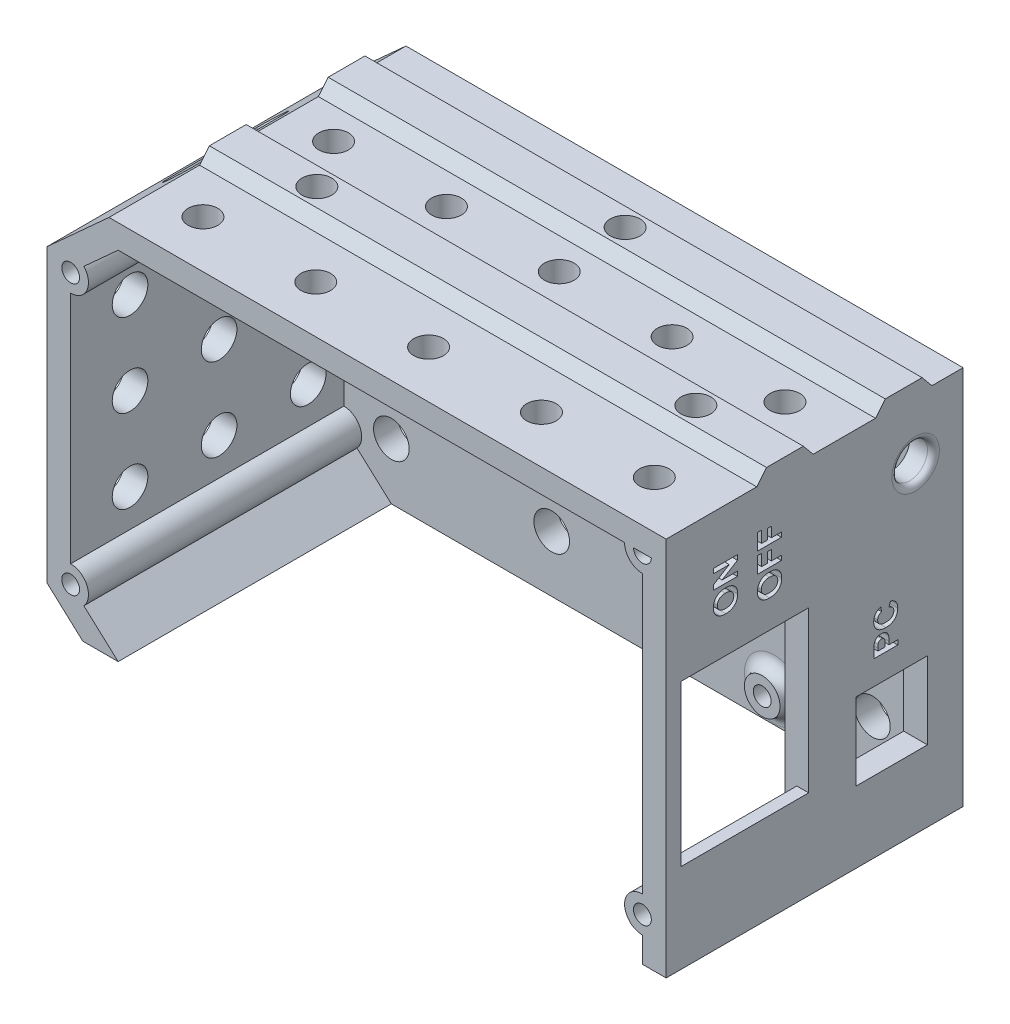
SolidWorks part; units mm, degrees
ref_plane "Спереди" through (0, 0, 0) normal (0, 0, 1) x (1, 0, 0)
ref_plane "Сверху" through (0, 0, 0) normal (0, 1, 0) x (1, 0, 0)
ref_plane "Справа" through (0, 0, 0) normal (1, 0, 0) x (0, 0, -1)
sketch "Эскиз1" plane through (0, 0, 0) normal (0, 0, 1) x (1, 0, 0)
  line L1 (-45, 30) -> (45, 30)
  line L2 (-45, 30) -> (-45, -30)
  line L3 (-45, -30) -> (45, -30)
  line L4 (45, 30) -> (45, -30)
  line L5 (-45, 30) -> (45, -30) construction
  line L6 (-45, -30) -> (45, 30) construction
  point P0 (0, 0)
  dimension "D1" = 60
  dimension "D2" = 90
extrude "Бобышка-Вытянуть1" add sketch "Эскиз1" along normal blind 4
sketch "Эскиз2" plane through (0, 0, 4) normal (0, 0, 1) x (1, 0, 0)
  line L0 (-45, -30) -> (-45, -10)
  line L1 (-45, 30) -> (-45, -30) construction
  line L2 (-45, -10) -> (45, -10)
  line L3 (45, -30) -> (45, 30) construction
  line L4 (-45, -10) -> (-38, -10)
  circle A0 centre (-38, -10) radius 1.5
  dimension "D3" = 3
  dimension "D1" = 20
  dimension "D2" = 7
extrude "Вырез-Вытянуть2" cut sketch "Эскиз2" against normal blind 10 contours L2 A0 L4 | L4 A0 L2
sketch "Эскиз3" plane through (0, 0, 4) normal (0, 0, 1) x (1, 0, 0)
  line L0 (-38, -10) -> (-38, 16.74)
  circle A0 centre (-38, 16.74) radius 1.5
  dimension "D2" = 3
  dimension "D1" = 26.74
extrude "Вырез-Вытянуть8" cut sketch "Эскиз3" against normal blind 10
sketch "Эскиз6" plane through (0, 0, 4) normal (0, 0, 1) x (1, 0, 0)
  line L0 (-38, 16.74) -> (-38, 21.13)
  line L1 (-38, 21.13) -> (13.37, 21.13)
  circle A0 centre (13.37, 21.13) radius 1.5
  dimension "D3" = 3
  dimension "D1" = 4.39
  dimension "D2" = 51.37
extrude "Вырез-Вытянуть9" cut sketch "Эскиз6" against normal blind 10
sketch "Эскиз7" plane through (0, 0, 4) normal (0, 0, 1) x (1, 0, 0)
  line L0 (-38, -10) -> (-38, -24.81)
  line L1 (-38, -24.81) -> (12.45, -24.81)
  circle A0 centre (12.45, -24.81) radius 1.5
  dimension "D3" = 3
  dimension "D1" = 14.81
  dimension "D2" = 50.45
extrude "Вырез-Вытянуть10" cut sketch "Эскиз7" against normal blind 10 contours A0
sketch "Эскиз8" plane through (0, 0, 4) normal (0, 0, 1) x (1, 0, 0)
  circle A0 centre (-38, 16.74) radius 3
  circle A1 centre (-38, -10) radius 3
  circle A2 centre (13.37, 21.13) radius 3
  circle A3 centre (12.45, -24.81) radius 3
  dimension "D1" = 6
extrude "Бобышка-Вытянуть2" add sketch "Эскиз8" along normal blind 4
fillet "Скругление1" radius 2 4 edges at (16.37, 21.13, 4) (-35, 16.74, 4) (-35, -10, 4) (15.45, -24.81, 4)
sketch "Эскиз9" plane through (0, 0, 0) normal (0, 0, -1) x (-1, 0, 0)
  circle A0 centre (-12.45, -24.81) radius 1.5
  circle A1 centre (38, -10) radius 1.5
  circle A2 centre (38, 16.74) radius 1.5
  circle A3 centre (-13.37, 21.13) radius 1.5
  dimension "D1" = 3
extrude "Вырез-Вытянуть11" cut sketch "Эскиз9" against normal through all
sketch "Эскиз10" plane through (0, 0, 0) normal (0, 0, -1) x (-1, 0, 0)
  line L0 (45, -30) -> (-45, -30) construction
  line L1 (-14.0377, -22.06) -> (-15.6254, -24.81)
  line L2 (-15.6254, -24.81) -> (-14.0377, -27.56)
  line L3 (-14.0377, -27.56) -> (-10.8623, -27.56)
  line L4 (-10.8623, -27.56) -> (-9.2746, -24.81)
  line L5 (-9.2746, -24.81) -> (-10.8623, -22.06)
  line L6 (-10.8623, -22.06) -> (-14.0377, -22.06)
  line L7 (-45, 30) -> (45, 30) construction
  line L8 (-14.9577, 23.88) -> (-16.5454, 21.13)
  line L9 (-16.5454, 21.13) -> (-14.9577, 18.38)
  line L10 (-14.9577, 18.38) -> (-11.7823, 18.38)
  line L11 (-11.7823, 18.38) -> (-10.1946, 21.13)
  line L12 (-10.1946, 21.13) -> (-11.7823, 23.88)
  line L13 (-11.7823, 23.88) -> (-14.9577, 23.88)
  line L14 (36.4123, 19.49) -> (34.8246, 16.74)
  line L15 (34.8246, 16.74) -> (36.4123, 13.99)
  line L16 (36.4123, 13.99) -> (39.5877, 13.99)
  line L17 (39.5877, 13.99) -> (41.1754, 16.74)
  line L18 (41.1754, 16.74) -> (39.5877, 19.49)
  line L19 (39.5877, 19.49) -> (36.4123, 19.49)
  line L20 (36.4123, -7.25) -> (34.8246, -10)
  line L21 (34.8246, -10) -> (36.4123, -12.75)
  line L22 (36.4123, -12.75) -> (39.5877, -12.75)
  line L23 (39.5877, -12.75) -> (41.1754, -10)
  line L24 (41.1754, -10) -> (39.5877, -7.25)
  line L25 (39.5877, -7.25) -> (36.4123, -7.25)
  circle A0 centre (-12.45, -24.81) radius 2.75 construction
  circle A1 centre (-13.37, 21.13) radius 2.75 construction
  circle A2 centre (38, 16.74) radius 2.75 construction
  circle A3 centre (38, -10) radius 2.75 construction
  dimension "D1" = 5.5
  dimension "D2" = 5.5
  dimension "D3" = 5.5
  dimension "D4" = 5.5
extrude "Вырез-Вытянуть12" cut sketch "Эскиз10" against normal blind 2.5
sketch "Эскиз11" plane through (0, 0, 8) normal (0, 0, 1) x (1, 0, 0)
  line L1 (-45, 30) -> (45, 30)
  line L2 (-45, 30) -> (-45, -30)
  line L3 (-45, -30) -> (45, -30)
  line L4 (45, 30) -> (45, -30)
extrude "Вырез-Вытянуть13" cut sketch "Эскиз11" against normal blind 2
sketch "Эскиз12" plane through (0, 0, 4) normal (0, 0, 1) x (1, 0, 0)
  line L0 (-45, 30) -> (-52, 30)
  line L1 (-52, 30) -> (-60, 22.735)
  line L2 (-60, 22.735) -> (-60, -22.735)
  line L3 (-60, -22.735) -> (-52, -30)
  line L4 (-52, -30) -> (-45, -30)
  line L5 (-45, 30) -> (-45, -30) construction
  line L6 (-45, 30) -> (-45, -30)
  dimension "D1" = 7
  dimension "D2" = 15
extrude "Бобышка-Вытянуть4" add sketch "Эскиз12" against normal blind 4
sketch "Эскиз14" plane through (0, 0, 4) normal (0, 0, 1) x (1, 0, 0)
  line L0 (-52, -30) -> (-60, -22.735)
  line L1 (-60, -22.735) -> (-60, 22.735)
  line L2 (-60, 22.735) -> (-52, 30)
  line L4 (-54.6891, 32.9612) -> (-64, 24.5058)
  line L5 (-64, 24.5058) -> (-64, -24.5058)
  line L6 (-64, -24.5058) -> (-54.6891, -32.9612)
  line L8 (36.2748, 30) -> (-52, 30)
  line L9 (40.2748, 34) -> (40.2748, -32.9612)
  line L10 (40.2748, -32.9612) -> (36.2748, -32.9612)
  line L11 (36.2748, -32.9612) -> (36.2748, 30)
  line L12 (45, 30) -> (-52, 30) construction
  line L13 (36.2748, 30) -> (-52, 30)
  line L14 (40.2748, 34) -> (26.8703, 34)
  line L15 (26.8703, 34) -> (-76.5802, 34)
  line L16 (-54.6891, 32.9612) -> (-53.5452, 34)
  line L17 (-52, -30) -> (-52, -32.9612)
  line L18 (-52, -32.9612) -> (-54.6891, -32.9612)
  line M13 (45, 30) -> (-52, 30)
  line M14 (-52, 30) -> (-60, 22.735)
  line M15 (-60, 22.735) -> (-60, -22.735)
  line M16 (-60, -22.735) -> (-52, -30)
  line M17 (-52, -30) -> (45, -30)
  dimension "D1" = 4
  dimension "D2" = 4
  dimension "D3" = 4
  dimension "D4" = 4
  dimension "D5" = 4
extrude "Бобышка-Вытянуть7" add sketch "Эскиз14" along normal blind 47 and the other way blind 4 contours L18 L17 L9 L14 L15 L16 L4 L5 L6 M16 M15 M14 M13 | L11 L9 M17 M13
sketch "Эскиз17" plane through (0, 0, 0) normal (0, 0, -1) x (-1, 0, 0)
  line L0 (52, -30) -> (63.4859, -30)
  line L1 (63.4859, -30) -> (63.4859, -35.9057)
  line L2 (63.4859, -35.9057) -> (48.8833, -35.9057)
  line L3 (48.8833, -35.9057) -> (52, -30)
extrude "Вырез-Вытянуть15" cut sketch "Эскиз17" against normal through all
sketch "Эскиз18" plane through (0, 0, 0) normal (0, 0, -1) x (-1, 0, 0)
  line L1 (-45, -30) -> (-40.2748, -30)
  line L2 (-45, -30) -> (-45, 34)
  line L3 (-45, 34) -> (-40.2748, 34)
  line L4 (-40.2748, -30) -> (-40.2748, 34)
extrude "Вырез-Вытянуть16" cut sketch "Эскиз18" against normal through all
sketch "Эскиз20" plane through (0, 0, 51) normal (0, 0, 1) x (1, 0, 0)
  line L1 (-68.2463, 36.8507) -> (47.1155, 36.8507)
  line L2 (-68.2463, 36.8507) -> (-68.2463, -36.3098)
  line L3 (-68.2463, -36.3098) -> (47.1155, -36.3098)
  line L4 (47.1155, 36.8507) -> (47.1155, -36.3098)
extrude "Вырез-Вытянуть17" cut sketch "Эскиз20" against normal blind 1
sketch "Эскиз21" plane through (-41.1216, 45.2821, 0) normal (-0.6723, 0.7403, 0) x (0.7403, 0.6723, 0)
  line L0 (-16.7819, -50) -> (-21.2819, -50)
  line L1 (-16.7819, -50) -> (-30.9043, -50) construction
  line L2 (-21.2819, -50) -> (-21.2819, -35)
  line L3 (-16.7819, 0) -> (-16.7819, -50) construction
  line L4 (-30.9043, -50) -> (-30.9043, -35)
  line L5 (-26.7819, -35) -> (-21.2819, -35)
  line L7 (-30.9043, 0) -> (-30.9043, -50) construction
  line L8 (-21.2819, -35) -> (-21.2819, -15)
  line L9 (-21.2819, -15) -> (-26.7819, -15)
  line L10 (-26.7819, -15) -> (-26.7819, -35)
  dimension "D1" = 15
  dimension "D2" = 4.5
  dimension "D3" = 5.5
  dimension "D4" = 20
extrude "Вырез-Вытянуть18" cut sketch "Эскиз21" against normal up to next contours L9 L10 L5 L8
fillet "Скругление2" radius 2.75 4 edges at (-55.532, 29.4941, 35) (-59.6036, 25.7966, 35) (-58.9124, 29.126, 35) (-56.2232, 26.1648, 35)
fillet "Скругление3" radius 2.75 4 edges at (-59.6036, 25.7966, 15) (-55.532, 29.4941, 15) (-58.9124, 29.126, 15) (-56.2232, 26.1648, 15)
sketch "Эскиз22" plane through (0, 0, 50) normal (0, 0, 1) x (1, 0, 0)
  line L0 (36.2748, 30) -> (36.2748, -30) construction
  circle A0 centre (-60, -22.735) radius 3
  circle A1 centre (-60, 22.735) radius 3
  circle A2 centre (36.2748, 30) radius 3
  circle A3 centre (36.2748, -22.735) radius 3
  dimension "D1" = 6
extrude "Бобышка-Вытянуть8" add sketch "Эскиз22" against normal up to next
sketch "Эскиз23" plane through (0, 0, 50) normal (0, 0, 1) x (1, 0, 0)
  circle A0 centre (-60, -22.735) radius 1.5
  circle A1 centre (-60, 22.735) radius 1.5
  circle A2 centre (36.2748, 30) radius 1.5
  circle A3 centre (36.2748, -22.735) radius 1.5
  dimension "D1" = 3
extrude "Вырез-Вытянуть19" cut sketch "Эскиз23" against normal blind 10
sketch "Эскиз24" plane through (40.2748, 0, 0) normal (1, 0, 0) x (0, 0, -1)
  line L0 (0, -30) -> (-6, -30)
  line L1 (0, -30) -> (-50, -30) construction
  line L2 (-6, -30) -> (-6, -18)
  line L3 (-6, -5) -> (-6, 34)
  line L4 (-6, -18) -> (-6, -5)
  line L5 (-6, -5) -> (-18, -5)
  line L6 (-18, -5) -> (-18, -18)
  line L7 (-18, -18) -> (-6, -18)
  line L8 (0, 34) -> (-6, 34)
  line L9 (0, 34) -> (-50, 34) construction
  line L10 (-6, 34) -> (-6, 24)
  circle A0 centre (-6, 24) radius 3
  dimension "D3" = 6
  dimension "D1" = 6
  dimension "D2" = 10
  dimension "D4" = 6
  dimension "D5" = 12
  dimension "D6" = 13
  dimension "D7" = 0
  dimension "D8" = 12
extrude "Вырез-Вытянуть23" cut sketch "Эскиз24" against normal blind 10 contours L6 L7 L4 L5
sketch "Эскиз25" plane through (40.2748, 0, 0) normal (1, 0, 0) x (0, 0, -1)
  text T0 "<b>PC</b>"
extrude "Вырез-Вытянуть24" cut sketch "Эскиз25" against normal blind 10
sketch "Эскиз26" plane through (40.2748, 0, 0) normal (1, 0, 0) x (0, 0, -1)
  line L0 (0, 34) -> (-17, 34)
  line L1 (0, 34) -> (-50, 34) construction
  line L2 (-17, 34) -> (-17, 24)
  line L3 (-17, 24) -> (-44, 24)
  line L4 (-44, 24) -> (-44, 2.5)
  line L5 (-44, 2.5) -> (-17, 2.5)
  line L6 (-17, 2.5) -> (-17, 24)
  line L7 (0, 34) -> (0, 24)
  line L8 (0, 34) -> (0, -30) construction
  line L9 (0, 24) -> (-8, 24)
  circle A0 centre (-8, 24) radius 3
  dimension "D5" = 10
  dimension "D1" = 17
  dimension "D2" = 10
  dimension "D3" = 27
  dimension "D4" = 21.5
  dimension "D6" = 8
extrude "Вырез-Вытянуть25" cut sketch "Эскиз26" against normal blind 10
sketch "Эскиз27" plane through (40.2748, 0, 0) normal (1, 0, 0) x (0, 0, -1)
  text T0 "<b>ON/OFF</b>" font "Arial" height in points 12
extrude "Вырез-Вытянуть27" cut sketch "Эскиз27" against normal blind 10
sketch "Эскиз29" plane through (0, 34, 0) normal (0, 1, 0) x (1, 0, 0)
  line L0 (40.2748, 0) -> (40.2748, -10)
  line L1 (40.2748, 0) -> (40.2748, -50) construction
  line L2 (40.2748, -10) -> (40.2748, -40)
  line L3 (40.2748, -40) -> (40.2748, -50)
  line L4 (40.2748, -10) -> (40.2748, -5.25)
  line L5 (40.2748, -10) -> (-53.5452, -10)
  line L6 (-53.5452, 0) -> (-53.5452, -50) construction
  line L7 (40.2748, -25) -> (-53.5452, -25) construction
  line L8 (40.2748, -10) -> (40.2748, -14.75)
  line L9 (40.2748, -14.75) -> (-53.5452, -14.75)
  line L10 (-53.5452, -14.75) -> (-53.5452, -5.25)
  line L11 (-53.5452, -5.25) -> (40.2748, -5.25)
  line L12 (-53.5452, -44.75) -> (40.2748, -44.75)
  line L13 (40.2748, -35.25) -> (-53.5452, -35.25)
  line L14 (40.2748, -44.75) -> (40.2748, -35.25)
  line L15 (-53.5452, -35.25) -> (-53.5452, -44.75)
  line M6 (-53.5452, 0) -> (-53.5452, -50)
  line M8 (40.2748, -50) -> (40.2748, 0)
  dimension "D1" = 10
  dimension "D2" = 4.75
  dimension "D3" = 4.75
extrude "Бобышка-Вытянуть9" add sketch "Эскиз29" along normal blind 2 contours L13 L12 L3 M8 M6 | L9 L2 L5 M6 | L11 L5 M6 M8
sketch "Эскиз30" plane through (40.2748, 0, 0) normal (1, 0, 0) x (0, 0, -1)
  line L0 (-44.75, 34) -> (-43.1, 36)
  line L1 (-44.75, 36) -> (-35.25, 36) construction
  line L2 (-44.75, 34) -> (-44.75, 36)
  line L3 (-44.75, 36) -> (-43.1, 36)
  line L4 (-40, 36) -> (-43.1, 36)
  line L5 (-40, 36) -> (-40, 33.3425)
  line L6 (-35.25, 36) -> (-36.9, 36)
  line L7 (-35.25, 34) -> (-35.25, 36)
  line L8 (-35.25, 34) -> (-36.9, 36)
  line L9 (-25, 34) -> (-25, 29.2128)
  line L10 (-14.75, 34) -> (-35.25, 34) construction
  line L11 (-14.75, 34) -> (-13.1, 36)
  line L12 (-14.75, 34) -> (-14.75, 36)
  line L13 (-14.75, 36) -> (-13.1, 36)
  line L14 (-10, 36) -> (-10, 33.3425)
  line L15 (-10, 36) -> (-6.9, 36)
  line L16 (-5.25, 36) -> (-6.9, 36)
  line L17 (-5.25, 34) -> (-5.25, 36)
  line L18 (-5.25, 34) -> (-6.9, 36)
  dimension "D1" = 3.1
extrude "Вырез-Вытянуть28" cut sketch "Эскиз30" against normal through all contours L8 L7 L6 | L3 L2 L0 | L13 L12 L11 | L18 L17 L16
sketch "Эскиз31" plane through (36.2748, 0, 0) normal (-1, 0, 0) x (0, 0, 1)
  line L0 (30.5, 2.5) -> (47, 2.5)
  line L2 (44, 2.5) -> (17, 2.5) construction
  line L3 (30.5, 2.5) -> (14, 2.5)
  line L4 (17, 24) -> (47, 24)
  line L5 (47, 24) -> (47, 2.5)
  line L6 (14, 2.5) -> (14, 24)
  line L7 (14, 24) -> (17, 24)
  dimension "D1" = 16.5
extrude "Вырез-Вытянуть29" cut sketch "Эскиз31" against normal blind 2
sketch "Эскиз32" plane through (0, 36, 0) normal (0, 1, 0) x (1, 0, 0)
  line L0 (40.2748, -40) -> (25.2748, -40)
  line L1 (-53.5452, -10) -> (40.2748, -10)
  line L2 (-53.5452, -5.25) -> (-53.5452, -14.75) construction
  line L3 (40.2748, -43.1) -> (40.2748, -36.9) construction
  line L4 (-53.5452, -40) -> (-38.5452, -40)
  line L5 (-53.5452, -36.9) -> (-53.5452, -43.1) construction
  line L6 (-53.5452, -25) -> (-45.8165, -25)
  line L7 (-53.5452, -14.75) -> (-53.5452, -35.25) construction
  line L8 (40.2748, -13.1) -> (40.2748, -6.9) construction
  circle A0 centre (-38.5452, -40) radius 2.5
  circle A1 centre (25.2748, -40) radius 2.5
  circle A2 centre (-6.6352, -10) radius 2.5
  dimension "D2" = 5
  dimension "D1" = 15
extrude "Вырез-Вытянуть32" cut sketch "Эскиз32" against normal through all
sketch "Эскиз34" plane through (0, 30, 0) normal (0, -1, 0) x (1, 0, 0)
  circle A0 centre (-38.5452, 40) radius 4.5
  circle A1 centre (-6.6352, 10) radius 4.5
  circle A2 centre (25.2748, 40) radius 4.5
  dimension "D1" = 9
extrude "Вырез-Вытянуть33" cut sketch "Эскиз34" against normal blind 1
fillet "Скругление5" radius 1 3 edges at (-38.5452, 30, 35.5) (-6.6352, 30, 5.5) (25.2748, 30, 35.5)
fillet "Скругление6" radius 1 1 edges at (40.2748, 27, 8)
sketch "Эскиз36" plane through (0, 0, 0) normal (0, 0, -1) x (-1, 0, 0)
  line L0 (64, -24.5058) -> (64, -20.5058)
  line L1 (64, 24.5058) -> (64, -24.5058) construction
  line L2 (64, -20.5058) -> (52, -20.5058)
  circle A0 centre (52, -20.5058) radius 3
  circle A1 centre (25, -20.5058) radius 3
  circle A2 centre (-2, -20.5058) radius 3
  circle A3 centre (-29, -20.5058) radius 3
  circle A4 centre (25, 1.4942) radius 3
  circle A5 centre (-2, 1.4942) radius 3
  circle A6 centre (-29, 1.4942) radius 3
  circle A7 centre (25, 23.4942) radius 3
  circle A8 centre (-2, 23.4942) radius 3
  circle A9 centre (-29, 23.4942) radius 3
  circle A10 centre (52, 1.4942) radius 3
  circle A11 centre (52, 23.4942) radius 3
  dimension "D3" = 6
  dimension "D1" = 4
  dimension "D2" = 12
  dimension "D4" = 4
  dimension "D5" = 3
extrude "Вырез-Вытянуть34" cut sketch "Эскиз36" against normal blind 5
sketch "Эскиз37" plane through (0, 0, 0) normal (0, 0, -1) x (-1, 0, 0)
  line L0 (52, -20.5058) -> (52, 1.4942)
  line L1 (52, -9.5058) -> (24.8602, -9.5058)
  circle A0 centre (38.4301, -9.5058) radius 3
  circle A1 centre (10.4301, -9.5058) radius 3
  circle A2 centre (-17.5699, -9.5058) radius 3
  circle A3 centre (10.4301, 12.4942) radius 3
  circle A4 centre (-17.5699, 12.4942) radius 3
  circle A5 centre (38.4301, 12.4942) radius 3
  dimension "D1" = 6
  dimension "D2" = 3
  dimension "D3" = 2
extrude "Вырез-Вытянуть35" cut sketch "Эскиз37" against normal blind 5 contours A1 | A2 | A4 | A3
sketch "Эскиз38" plane through (-64, 0, 0) normal (-1, 0, 0) x (0, 0, 1)
  line L0 (50, 24.5058) -> (40, 24.5058)
  line L1 (0, 24.5058) -> (50, 24.5058) construction
  line L2 (40, 24.5058) -> (40, 14.5058)
  circle A0 centre (40, 14.5058) radius 3
  circle A1 centre (25, 14.5058) radius 3
  circle A2 centre (10, 14.5058) radius 3
  circle A3 centre (25, 0.5058) radius 3
  circle A4 centre (10, 0.5058) radius 3
  circle A5 centre (25, -13.4942) radius 3
  circle A6 centre (10, -13.4942) radius 3
  circle A7 centre (40, 0.5058) radius 3
  circle A8 centre (40, -13.4942) radius 3
  dimension "D3" = 6
  dimension "D1" = 10
  dimension "D2" = 10
  dimension "D4" = 3
  dimension "D5" = 3
extrude "Вырез-Вытянуть36" cut sketch "Эскиз38" against normal blind 5
sketch "Эскиз39" plane through (0, 34, 0) normal (0, 1, 0) x (1, 0, 0)
  line L0 (40.2748, -35.25) -> (40.2748, -30.25)
  line L1 (40.2748, -14.75) -> (40.2748, -35.25) construction
  line L2 (40.2748, -30.25) -> (30.2748, -30.25)
  line L3 (30.2748, -30.25) -> (30.2748, -30.5973)
  circle A0 centre (30.2748, -30.5973) radius 2
  circle A1 centre (15.2748, -30.5973) radius 2
  circle A2 centre (0.2748, -30.5973) radius 2
  circle A3 centre (-14.7252, -30.5973) radius 2
  circle A4 centre (-29.7252, -30.5973) radius 2
  circle A5 centre (-44.7252, -30.5973) radius 2
  circle A6 centre (15.2748, -18.5973) radius 2
  circle A7 centre (0.2748, -18.5973) radius 2
  circle A8 centre (-14.7252, -18.5973) radius 2
  circle A9 centre (-29.7252, -18.5973) radius 2
  circle A10 centre (-44.7252, -18.5973) radius 2
  circle A11 centre (30.2748, -18.5973) radius 2
  dimension "D3" = 4
  dimension "D1" = 5
  dimension "D2" = 10
  dimension "D4" = 6
  dimension "D5" = 2
extrude "Вырез-Вытянуть37" cut sketch "Эскиз39" against normal blind 5
sketch "Эскиз41" plane through (0, 34, 0) normal (0, 1, 0) x (1, 0, 0)
  line L1 (40.2748, -50) -> (-53.5452, -50)
  line L2 (40.2748, -50) -> (40.2748, -14.75)
  line L3 (40.2748, -14.75) -> (-53.5452, -14.75)
  line L4 (-53.5452, -50) -> (-53.5452, -14.75)
extrude "Бобышка-Вытянуть10" add sketch "Эскиз41" against normal blind 4
sketch "Эскиз42" plane through (0, 36, 0) normal (0, 1, 0) x (1, 0, 0)
  line L1 (40.2748, -44.75) -> (-53.5452, -44.75)
  line L2 (40.2748, -44.75) -> (40.2748, -35.25)
  line L3 (40.2748, -35.25) -> (-53.5452, -35.25)
  line L4 (-53.5452, -44.75) -> (-53.5452, -35.25)
extrude "Вырез-Вытянуть38" cut sketch "Эскиз42" against normal blind 2
sketch "Эскиз43" plane through (0, 34, 0) normal (0, 1, 0) x (1, 0, 0)
  line L0 (40.2748, -10) -> (40.2748, -30)
  line L1 (40.2748, -13.1) -> (40.2748, -6.9) construction
  line L2 (40.2748, -14.75) -> (40.2748, -50) construction
  line L3 (40.2748, -30) -> (40.2748, -25.014)
  line L4 (40.2748, -30) -> (40.2748, -34.75)
  line L5 (40.2748, -30) -> (30.5786, -30)
  line L6 (40.2748, -34.75) -> (-53.5452, -34.75)
  line L7 (-53.5452, -14.75) -> (-53.5452, -50) construction
  line L8 (40.2748, -25.25) -> (-53.5452, -25.25)
  line L9 (-53.5452, -34.75) -> (-53.5452, -25.25)
  line L10 (40.2748, -34.75) -> (40.2748, -25.25)
  dimension "D1" = 20
  dimension "D2" = 4.75
extrude "Бобышка-Вытянуть11" add sketch "Эскиз43" along normal blind 2
sketch "Эскиз44" plane through (40.2748, 0, 0) normal (1, 0, 0) x (0, 0, -1)
  line L0 (-20, 34) -> (-20, 32.0231)
  line L1 (-14.75, 34) -> (-25.25, 34) construction
  line L2 (-14.75, 34) -> (-13.1, 36)
  line L3 (-5.25, 34) -> (-6.9, 36)
  line L4 (-34.75, 34) -> (-33.1, 36)
  line L5 (-25.25, 34) -> (-26.9, 36)
  line L6 (-34.75, 34) -> (-34.75, 36)
  line L7 (-34.75, 36) -> (-33.1, 36)
  line L8 (-25.25, 36) -> (-25.25, 34)
  line L9 (-26.9, 36) -> (-25.25, 36)
extrude "Вырез-Вытянуть39" cut sketch "Эскиз44" against normal through all contours L7 L6 L4 | L9 L5 L8
sketch "Эскиз45" plane through (0, 36, 0) normal (0, 1, 0) x (1, 0, 0)
  line L0 (40.2748, -30) -> (25.2748, -30)
  line L1 (40.2748, -33.1) -> (40.2748, -26.9) construction
  line L2 (-53.5452, -30) -> (-38.5452, -30)
  line L3 (-53.5452, -26.9) -> (-53.5452, -33.1) construction
  circle A0 centre (25.2748, -30) radius 2.5
  circle A1 centre (-38.5452, -30) radius 2.5
  dimension "D2" = 5
  dimension "D1" = 15
extrude "Вырез-Вытянуть40" cut sketch "Эскиз45" against normal blind 10
sketch "Эскиз46" plane through (0, 30, 0) normal (0, -1, 0) x (1, 0, 0)
  circle A0 centre (25.2748, 30) radius 4.5
  circle A1 centre (-38.5452, 30) radius 4.5
  circle A2 centre (-6.6352, 10) radius 4.5
  dimension "D1" = 9
  dimension "D2" = 9
  dimension "D3" = 9
extrude "Вырез-Вытянуть41" cut sketch "Эскиз46" against normal blind 2
fillet "Скругление7" radius 1 2 edges at (25.2748, 30, 25.5) (-38.5452, 30, 25.5)
sketch "Эскиз47" plane through (0, 30, 0) normal (0, -1, 0) x (1, 0, 0)
  circle A0 centre (-6.6352, 10) radius 5.5
  circle A1 centre (-6.6352, 10) radius 2.5
  dimension "D1" = 5
extrude "Бобышка-Вытянуть13" add sketch "Эскиз47" against normal blind 2
sketch "Эскиз48" plane through (0, 30, 0) normal (0, -1, 0) x (1, 0, 0)
  circle A0 centre (-6.6352, 10) radius 4.5
  dimension "D1" = 9
extrude "Вырез-Вытянуть42" cut sketch "Эскиз48" against normal blind 2
fillet "Скругление8" radius 1 1 edges at (-6.6352, 30, 5.5)
sketch "Эскиз49" plane through (0, 34, 0) normal (0, 1, 0) x (1, 0, 0)
  line L0 (40.2748, -20) -> (30.2748, -20)
  line L1 (40.2748, -14.75) -> (40.2748, -25.25) construction
  circle A0 centre (30.2748, -20) radius 2.5
  circle A1 centre (11.2748, -20) radius 2.5
  circle A2 centre (-7.7252, -20) radius 2.5
  circle A3 centre (-26.7252, -20) radius 2.5
  circle A4 centre (-45.7252, -20) radius 2.5
  circle A5 centre (11.2748, -42) radius 2.5
  circle A6 centre (-7.7252, -42) radius 2.5
  circle A7 centre (-26.7252, -42) radius 2.5
  circle A8 centre (-45.7252, -42) radius 2.5
  circle A9 centre (30.2748, -42) radius 2.5
  dimension "D1" = 5
  dimension "D2" = 10
  dimension "D3" = 5
  dimension "D4" = 2
extrude "Вырез-Вытянуть43" cut sketch "Эскиз49" against normal through all
sketch "Эскиз50" plane through (40.2748, 0, 0) normal (1, 0, 0) x (0, 0, -1)
  line L0 (-14.75, 34) -> (-25.25, 34) construction
  line L1 (-50, -30) -> (-20, -30)
  line L2 (-50, -30) -> (-50, 34)
  line L3 (-50, 34) -> (-20, 34)
  line L4 (-20, -30) -> (-20, 0)
  line L5 (-20, 26.8869) -> (-20, 34)
  line L6 (-20, 0) -> (-13.5212, 0)
  line L7 (-50, -19.735) -> (-20, -19.735)
  line L8 (-20, 26.8869) -> (-13.5212, 26.8869)
  line L9 (-13.5212, 0) -> (-13.5212, 26.8869)
  line L10 (-20, 26.8869) -> (-50, 27)
extrude "Бобышка-Вытянуть14" add sketch "Эскиз50" against normal blind 4 contours L8 L10 L2 L7 L4 L6 L9
sketch "Эскиз51" plane through (40.2748, 0, 0) normal (1, 0, 0) x (0, 0, -1)
  line L0 (-50, -30) -> (-47.5, -30)
  line L1 (0, -30) -> (-50, -30) construction
  line L2 (-47.5, -30) -> (-47.5, -15)
  line L4 (-47.5, -15) -> (-26, -15)
  line L5 (-47.5, -15) -> (-47.5, 12)
  line L6 (-47.5, 12) -> (-26, 12)
  line L7 (-26, -15) -> (-26, 12)
  dimension "D1" = 2.5
  dimension "D2" = 15
  dimension "D3" = 21.5
  dimension "D4" = 27
extrude "Вырез-Вытянуть44" cut sketch "Эскиз51" against normal blind 4 contours L4 L7 L6 L5
sketch "Эскиз52" plane through (36.2748, 0, 0) normal (-1, 0, 0) x (0, 0, 1)
  line L0 (26, -15) -> (26, -18)
  line L1 (26, -18) -> (47.4825, -18)
  line L2 (47.4825, -18) -> (47.4825, 15)
  line L3 (47.4825, 15) -> (26, 15)
  line L4 (26, 15) -> (26, -18)
  line M4 (47.5, -15) -> (26, -15)
  line M5 (26, -15) -> (26, 12)
  line M6 (26, 12) -> (47.5, 12)
  dimension "D1" = 33
  dimension "D2" = 3
extrude "Вырез-Вытянуть45" cut sketch "Эскиз52" against normal blind 2 contours L1 L2 L0 M4 | L2 M4 M6 M5 | L3 L4 L2 M6
sketch "Эскиз53" plane through (40.2748, 0, 0) normal (1, 0, 0) x (0, 0, -1)
  text T0 "<b>PC</b>"
  text T1 "<b>ON</b>\r\n<b>OFF</b>"
extrude "Вырез-Вытянуть46" cut sketch "Эскиз53" against normal blind 2
